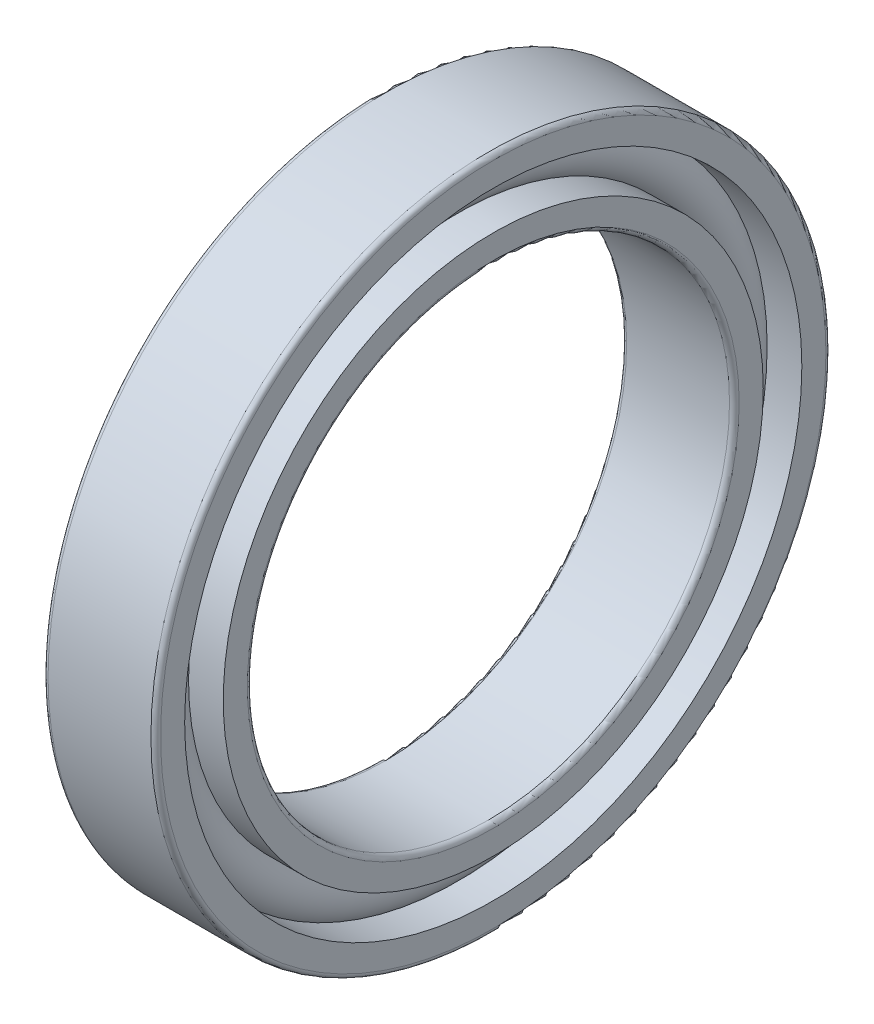
SolidWorks part; units mm, degrees
ref_plane "Plane1" through (0, 0, 0) normal (0, 0, 1) x (1, 0, 0)
ref_plane "Plane2" through (0, 0, 0) normal (0, 1, 0) x (1, 0, 0)
ref_plane "Plane3" through (0, 0, 0) normal (1, 0, 0) x (0, 0, -1)
sketch "Clipboard" plane through (0, 0, 0) normal (0, 0, 1) x (1, 0, 0)
  line L0 (-10, 0) -> (10, 0) construction
  line L1 (0, 0) -> (22.3471, -0.7804)
  line L2 (0, 0) -> (17.989, 0.6282)
  line L3 (0, 0) -> (22.3471, -0.7804)
  line L4 (0, 0) -> (-22.3573, -0.3902)
  dimension "BallCLRad" = 18
sketch "CagSpiSke" plane through (0, 0, 0) normal (0, 0, 1) x (1, 0, 0)
  line L0 (0.18, 17.7) -> (0.18, 18.3)
  line L1 (0.18, 18.3) -> (-0.18, 18.3)
  line L2 (-0.18, 18.3) -> (-0.18, 17.7)
  line L3 (-0.18, 17.7) -> (0.18, 17.7)
  line L4 (-20.6375, 0) -> (20.6375, 0) construction
  line L5 (0, 0) -> (0, 23.7692) construction
  dimension "OD" = 36.6
  dimension "ID" = 35.4
revolve "CageSpine" add sketch "CagSpiSke" angle 0.001 about L4 reverse direction yes
ref_axis "Axis1" through (-50, 0, 0) along (1, 0, 0)
sketch "CagBalSke" plane through (0, 0, 0) normal (0, 0, 1) x (1, 0, 0)
  line L0 (-1.98, 18) -> (1.98, 18)
  line L1 (-1.905, 18) -> (1.905, 18) construction
  line L2 (-10, 0) -> (10, 0) construction
  line L3 (0, 0) -> (0, 24) construction
  arc A0 (1.98, 18) -> (-1.98, 18) centre (0, 18) cw
  dimension "BallCLRad" = 18
revolve "CageBall" [suppressed] add sketch "CagBalSke" angle 360 about L1 reverse direction yes
pattern_circular "CageBalls" [suppressed] count 2 every 180 about axis through (-50, 0, 0) along (1, 0, 0)
sketch "CagTrmODSke" plane through (0, 0, 0) normal (0, 0, 1) x (1, 0, 0)
  line L0 (1.981, 18.3) -> (1.981, 19.981)
  line L1 (1.981, 19.981) -> (-1.981, 19.981)
  line L2 (-1.981, 19.981) -> (-1.981, 18.3)
  line L3 (-1.981, 18.3) -> (1.981, 18.3)
  line L4 (-20.6375, 0) -> (20.6375, 0) construction
  line L5 (0, 0) -> (0, 25) construction
  dimension "Width" = 3.962
  dimension "ID" = 36.6
  dimension "OD" = 39.962
revolve "CageTrimOD" [suppressed] cut sketch "CagTrmODSke" angle 360 about L4 reverse direction yes
sketch "CagTrmIDSke" plane through (0, 0, 0) normal (0, 0, 1) x (1, 0, 0)
  line L0 (1.981, 16.021) -> (1.981, 17.7)
  line L1 (1.981, 17.7) -> (-1.981, 17.7)
  line L2 (-1.981, 17.7) -> (-1.981, 16.021)
  line L3 (-1.981, 16.021) -> (1.981, 16.021)
  line L4 (-20.6375, 0) -> (20.6375, 0) construction
  line L5 (0, 0) -> (0, 25) construction
  dimension "Width" = 3.962
  dimension "ID" = 32.042
  dimension "OD" = 35.4
revolve "CageTrimID" [suppressed] cut sketch "CagTrmIDSke" angle 360 about L4 reverse direction yes
sketch "BalSimSke" plane through (0, 0, 0) normal (0, 0, 1) x (1, 0, 0)
  line L0 (-10, 0) -> (10, 0) construction
  line L1 (-10, 18) -> (10, 18) construction
  line L2 (0, 0) -> (0, 23) construction
  circle A0 centre (0, 18) radius 1.8
  dimension "BallCLRad" = 18
  dimension "Ball_diameter" = 3.6
revolve "BallsSimplified" add sketch "BalSimSke" angle 360 about L0
sketch "BalDetSke" plane through (0, 0, 0) normal (0, 0, 1) x (1, 0, 0)
  line L0 (-1.8, 18) -> (1.8, 18)
  line L1 (-1.905, 18) -> (1.905, 18) construction
  line L2 (0, 0) -> (0, 25) construction
  arc A0 (1.8, 18) -> (-1.8, 18) centre (0, 18) cw
  dimension "BallCLRad" = 18
  dimension "Ball_diameter" = 3.6
revolve "BallDetailed" [suppressed] add sketch "BalDetSke" angle 360 about L1 reverse direction yes
sketch "InnRacSke" plane through (0, 0, 0) normal (0, 0, 1) x (1, 0, 0)
  line L0 (-1.3079, 16.8) -> (-3.5, 16.8)
  line L1 (-3.5, 16.8) -> (-3.5, 15.3)
  line L2 (-3.2, 15) -> (3.2, 15)
  line L3 (3.5, 15.3) -> (3.5, 16.8)
  line L4 (3.5, 16.8) -> (1.3079, 16.8)
  line L5 (-20.6375, 0) -> (20.6375, 0) construction
  line L6 (0, 0) -> (0, 30) construction
  arc A0 (-3.5, 15.3) -> (-3.2, 15) centre (-3.2, 15.3) ccw
  arc A1 (3.2, 15) -> (3.5, 15.3) centre (3.2, 15.3) ccw
  arc A2 (1.3079, 16.8) -> (-1.3079, 16.8) centre (0, 18) cw
  dimension "BallCLRad" = 18
  dimension "Fillet_radius" = 0.3
  dimension "Ball_diameter" = 3.55
  dimension "ID" = 30
  dimension "OD" = 33.6
  dimension "Width" = 7
revolve "InnerRace" add sketch "InnRacSke" angle 360 about L5 reverse direction yes
sketch "OutRacSke" plane through (0, 0, 0) normal (0, 0, 1) x (1, 0, 0)
  line L0 (-1.3079, 19.2) -> (-3.5, 19.2)
  line L1 (-3.5, 19.2) -> (-3.5, 20.7)
  line L2 (-3.2, 21) -> (3.2, 21)
  line L3 (3.5, 20.7) -> (3.5, 19.2)
  line L4 (3.5, 19.2) -> (1.3079, 19.2)
  line L5 (-20.6375, 0) -> (20.6375, 0) construction
  line L6 (0, 0) -> (0, 30) construction
  arc A0 (-3.5, 20.7) -> (-3.2, 21) centre (-3.2, 20.7) cw
  arc A1 (3.2, 21) -> (3.5, 20.7) centre (3.2, 20.7) cw
  arc A2 (1.3079, 19.2) -> (-1.3079, 19.2) centre (0, 18) ccw
  dimension "BallCLRad" = 18
  dimension "Fillet_radius" = 0.3
  dimension "Ball_diameter" = 3.55
  dimension "Width" = 7
revolve "OuterRace" add sketch "OutRacSke" angle 360 about L5 reverse direction yes
pattern_circular "BallsDetailed" [suppressed] count 2 every 180 about axis through (-50, 0, 0) along (1, 0, 0)
equation "\"BallCLRad@Clipboard\" = ( \"OD@OutRacSke\" + \"ID@InnRacSke\" ) / 4"
equation "\"BallCLRad@BalSimSke\" = \"BallCLRad@Clipboard\""
equation "\"BallCLRad@BalDetSke\" = \"BallCLRad@Clipboard\""
equation "\"BallCLRad@InnRacSke\" = \"BallCLRad@Clipboard\""
equation "\"BallCLRad@OutRacSke\" = \"BallCLRad@Clipboard\""
equation "\"Ball_diameter@InnRacSke\" = \"Ball_diameter@BalDetSke\" - 0.05"
equation "\"Ball_diameter@OutRacSke\" = \"Ball_diameter@BalDetSke\" - 0.05"
equation "\"Ball_diameter@BalSimSke\" = \"Ball_diameter@BalDetSke\""
equation "\"Width@OutRacSke\" = \"Width@InnRacSke\""
equation "\"Fillet_radius@OutRacSke\" = \"Fillet_radius@InnRacSke\""
equation "\"Max_count@Clipboard\" = int( 3.14159265 / atn(( \"Ball_diameter@BalDetSke\" / 2) / sqr( \"BallCLRad@Clipboard\"  *  \"BallCLRad@Clipboard\" - ( \"Ball_diameter@BalDetSke\" / 2) *  ( \"Ball_diameter@BalDetSke\" / 2))))"
equation "\"Max_count@Clipboard\" = ((sgn( \"Max_count@Clipboard\" - \"Count@Clipboard\" )-1)*( \"Max_count@Clipboard\" - \"Count@Clipboard\" ))/-2+ \"Count@Clipboard\""
equation "\"Count@BallsDetailed\" = int( \"Show_count@Clipboard\" ) "
equation "\"Count@BallsDetailed\" = ((sgn( \"Count@BallsDetailed\" - \"Max_count@Clipboard\" )-1)*( \"Count@BallsDetailed\" - \"Max_count@Clipboard\" ))/-2+ \"Max_count@Clipboard\""
equation "\"Count@BallsDetailed\" = ((sgn( \"Count@BallsDetailed\" - \"Min_count@Clipboard\" )+1)*( \"Count@BallsDetailed\" - \"Min_count@Clipboard\"))/2 +\"Min_count@Clipboard\""
equation "\"Angle@BallsDetailed\" = 360.0 / \"Max_count@Clipboard\""
equation "\"BallCLRad@CagBalSke\" = \"BallCLRad@Clipboard\""
equation "\"Count@CageBalls\" = \"Count@BallsDetailed\""
equation "\"Angle@CageBalls\" = \"Angle@BallsDetailed\""
equation "\"Angle@CageSpine\" =  \"Angle@CageBalls\" * ( \"Count@CageBalls\" -1 + int( \"Count@CageBalls\" / \"Max_count@Clipboard\" ) )  + 0.001 -  int( \"Count@CageBalls\" / \"Max_count@Clipboard\" ) * 0.001"
equation "\"Angle@CageSpine\" =  \"Angle@CageSpine\" * int( \"Min_count@Clipboard\" / 2) + int(1 / \"Min_count@Clipboard\")  * 0.001"
equation "\"CageWallOD@CagBalSke\" =  \"Ball_diameter@BalDetSke\" * 1.1"
equation "\"Thickness@CagSpiSke\" =  \"Ball_diameter@BalDetSke\" * 0.1"
equation "\"OD@CagTrmODSke\" = \"BallCLRad@Clipboard\" * 2 + \"CageWallOD@CagBalSke\" + 0.002"
equation "\"ID@CagTrmODSke\" = \"BallCLRad@Clipboard\" * 2 + \"Ball_diameter@BalDetSke\" / 6"
equation "\"OD@CagTrmIDSke\" = \"BallCLRad@Clipboard\" * 2 - \"Ball_diameter@BalDetSke\" / 6"
equation "\"ID@CagTrmIDSke\" = \"BallCLRad@Clipboard\" * 2 - \"CageWallOD@CagBalSke\" + 0.002"
equation "\"OD@CagSpiSke\" = \"ID@CagTrmODSke\""
equation "\"ID@CagSpiSke\" = \"OD@CagTrmIDSke\""
equation "\"Width@CagTrmODSke\" = \"CageWallOD@CagBalSke\" + 0.002"
equation "\"Width@CagTrmIDSke\" = \"CageWallOD@CagBalSke\" + 0.002"
